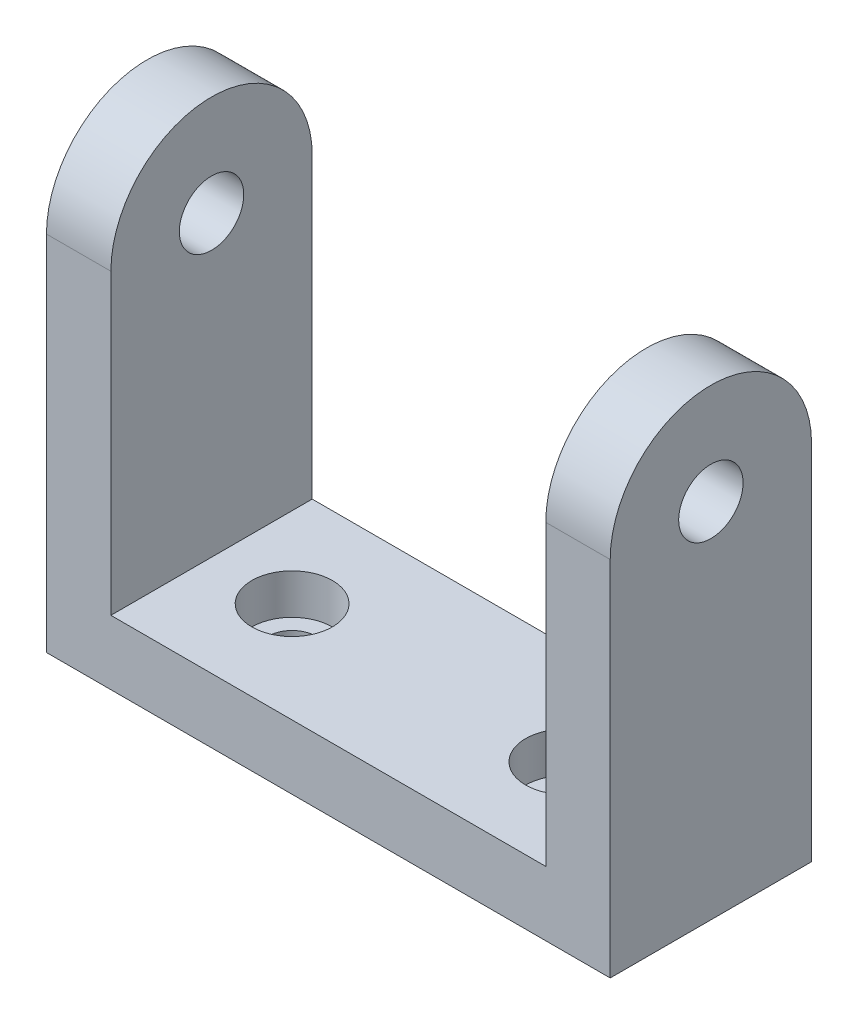
SolidWorks part; units mm, degrees
ref_plane "Front Plane" through (0, 0, 0) normal (0, 0, 1) x (1, 0, 0)
ref_plane "Top Plane" through (0, 0, 0) normal (0, 1, 0) x (1, 0, 0)
ref_plane "Right Plane" through (0, 0, 0) normal (1, 0, 0) x (0, 0, -1)
sketch "Sketch1" plane through (0, 0, 0) normal (0, 0, 1) x (1, 0, 0)
  line L0 (27, 0) -> (-27, 0)
  line L1 (-27, 0) -> (-27, 49.5)
  line L2 (-27, 49.5) -> (-35, 49.5)
  line L3 (-35, 49.5) -> (-35, -8)
  line L4 (-35, -8) -> (35, -8)
  line L5 (0, 9.0684) -> (0, -26.9429) construction
  line L6 (35, 49.5) -> (35, -8)
  line L7 (27, 49.5) -> (35, 49.5)
  line L8 (27, 0) -> (27, 49.5)
  line L9 (-27, 0) -> (-27, -8) construction
  point P10 (0, -8)
  point P13 (0, 0)
  dimension "D1" = 70
  dimension "D2" = 54
  dimension "D3" = 49.5
extrude "Boss-Extrude1" add sketch "Sketch1" along normal mid plane 25
fillet "Fillet1" 2 edges at (-31, 49.5, 12.5) (-31, 49.5, -12.5) type full round first side face at (0, 22.75, 12.5) second side face at (0, 22.75, -12.5) middle face at (-31, 49.5, 0)
fillet "Fillet2" 2 edges at (31, 49.5, -12.5) (31, 49.5, 12.5) type full round first side face at (0, 19.625, -12.5) second side face at (0, 19.625, 12.5) middle face at (31, 49.5, 0)
sketch "Sketch3" plane through (-35, 0, 0) normal (-1, 0, 0) x (0, 0, 1)
  circle A0 centre (0, 37) radius 4
  dimension "D1" = 8
extrude "Cut-Extrude1" cut sketch "Sketch3" against normal through all both and the other way through all
sketch "Sketch4" plane through (0, 0, 0) normal (0, 1, 0) x (1, 0, 0)
  line L0 (0, 0) -> (0, 19.3924) construction
  line L1 (-35, 12.5) -> (-35, -12.5) construction
  circle A0 centre (-17, 0) radius 3
  circle A1 centre (-17, 0) radius 5
  circle A2 centre (17, 0) radius 5
  circle A3 centre (17, 0) radius 3
  dimension "D1" = 10
  dimension "D2" = 6
  dimension "D3" = 18
extrude "Cut-Extrude4" cut sketch "Sketch4" against normal through all contours A0 | A3
extrude "Cut-Extrude6" cut sketch "Sketch4<4>" against normal blind 5 contours A2 | A1
sketch "Sketch4<4>" plane through (0, 0, 0) normal (0, 1, 0) x (1, 0, 0) same geometry as "Sketch4"
